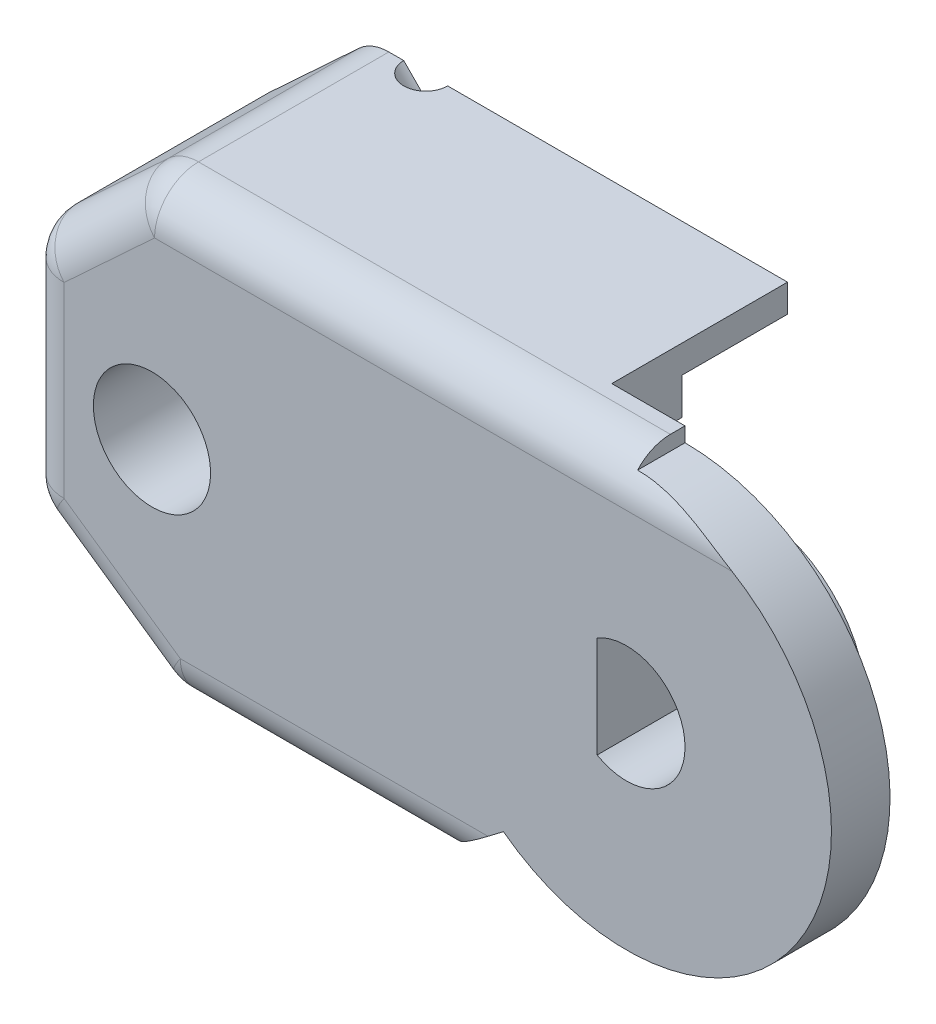
SolidWorks part; units mm, degrees
ref_plane "Front Plane" through (0, 0, 0) normal (0, 0, 1) x (1, 0, 0)
ref_plane "Top Plane" through (0, 0, 0) normal (0, 1, 0) x (1, 0, 0)
ref_plane "Right Plane" through (0, 0, 0) normal (1, 0, 0) x (0, 0, -1)
sketch "Sketch2" plane through (0, 0, 0) normal (0, 0, 1) x (1, 0, 0)
  line L1 (-2.5, 7.5) -> (-16.7, 7.5)
  line L2 (-20.7, 3.7934) -> (-20.7, -4.0316)
  line L3 (-15.7, -7.5) -> (-6.7, -7.5)
  line L4 (-6.7, -7.5) -> (-4.2, -5.6)
  line L5 (-2.5, 7.5) -> (0, 7.5)
  line L7 (0, 7) -> (0, 7.5)
  line L8 (-20.7, 3.7934) -> (-16.7, 7.5)
  line L9 (-20.7, -4.0316) -> (-15.7, -7.5)
  arc A1 (-4.2, -5.6) -> (7, 0) centre (0, 0) ccw
  arc A2 (7, 0) -> (0, 7) centre (0, 0) ccw
  dimension "D1" = 7
  dimension "D2" = 4
  dimension "D3" = 5
  dimension "D4" = 7.5
  dimension "D5" = 15
  dimension "D7" = 2.5
  dimension "D8" = 14
extrude "Boss-Extrude1" add sketch "Sketch2" along normal blind 2 contours A1 A2 L7 L5 L1 L8 L2 L9 L3 L4
sketch "Sketch4" plane through (0, 0, 2) normal (0, 0, 1) x (1, 0, 0)
  line L7 (-15.7, -7.5) -> (-6.7, -7.5)
  line L8 (-6.7, -7.5) -> (-6.7591, -4.5)
  line L9 (-6.7591, -4.5) -> (-12.2, -4.5)
  line L10 (-16.7, 7.5) -> (-2.5, 7.5)
  line L13 (-6.6963, 2) -> (-6.6963, 5.3)
  line L14 (-6.6963, 5.3) -> (-2.5, 5.3)
  line L21 (-20.7, -4.0316) -> (-15.7, -7.5)
  line L24 (-16.7, 7.5) -> (-20.7, 3.7934)
  line L25 (-20.7, -4.0316) -> (-20.7, 3.7934)
  line L26 (-12.2, 2) -> (-6.6963, 2)
  line L29 (-12.2, 2) -> (-12.2, -4.5)
  line L30 (-2.5, 7.5) -> (-2.5, 5.3)
  dimension "D1" = 8.5
  dimension "D2" = 2.5
  dimension "D3" = 3
extrude "Boss-Extrude2" add sketch "Sketch4" along normal blind 6
ref_point "Point1"
sketch "Sketch22" plane through (0, 0, 2) normal (0, 0, 1) x (1, 0, 0)
  line L0 (0, 5.3) -> (-14, 5.3) construction
  line L1 (0, 4) -> (-14, 4) construction
  line L2 (-14, 4) -> (-14, 5.3) construction
  circle A0 centre (0, 0) radius 5.3 construction
  circle A1 centre (0, 0) radius 4 construction
  dimension "D1" = 14
  dimension "D2" = 10.6
  dimension "D3" = 8
sketch "Sketch24" plane through (0, 0, 2) normal (0, 0, 1) x (1, 0, 0)
  circle A0 centre (0, 0) radius 3.9
  dimension "D1" = 7.8
extrude "Boss-Extrude5" add sketch "Sketch24" along normal blind 2.3
sketch "Sketch29" plane through (-6.6963, 0, 0) normal (1, 0, 0) x (0, 0, -1)
  line L0 (-1.9279, 3.9758) -> (-8, 3.9758) construction
  line L1 (-8, 2) -> (-8, 5.3) construction
sketch "Sketch30" plane through (-6.6963, 0, 0) normal (1, 0, 0) x (0, 0, -1)
  line L0 (-4.4659, 3.9758) -> (-4.4659, 5.3)
  line L1 (-4.4659, 3.9758) -> (-2.0573, 3.9758)
  line L2 (-4.4659, 5.3) -> (-2.0573, 5.3)
  line L3 (-2.0573, 3.9758) -> (-2.0573, 5.3)
  line L4 (-1.9279, 3.9758) -> (-8, 3.9758) construction
  line L5 (-8, 5.3) -> (-2, 5.3) construction
extrude "Cut-Extrude12" cut sketch "Sketch30" against normal blind 8
ref_plane "Plane1" through (0, 0, 8) normal (0, 0, 1) x (1, 0, 0)
sketch "Sketch8" plane through (0, 0, 2) normal (0, 0, 1) x (1, 0, 0)
  circle A1 centre (0, 0) radius 3.8
  circle A2 centre (0, 0) radius 2.5
sketch "Sketch28" plane through (0, 0, 4.3) normal (0, 0, 1) x (1, 0, 0)
  line L0 (-1, 1.7321) -> (-1, -1.7321)
  arc A0 (-1, -1.7321) -> (-1, 1.7321) centre (0, 0) ccw
  dimension "D1" = 1
  dimension "D2" = 2
extrude "Cut-Extrude11" cut sketch "Sketch28" against normal through all
sketch "Sketch33" plane through (0, 0, 8) normal (0, 0, 1) x (1, 0, 0)
  line L0 (-9.4481, 2) -> (-2.4157, -5.1566) construction
  line L1 (-12.2, 2) -> (-6.6963, 2) construction
  line L2 (-10.4836, -4.5) -> (-4.8246, 3.0469) construction
  line L3 (-6.7591, -4.5) -> (-12.2, -4.5) construction
fillet "Fillet1" radius 1.5 9 edges at (-11.2, -7.5, 0) (-8.35, 7.5, 0) (-18.7, 5.6467, 0) (-18.2, -5.7658, 0) (-20.7, -0.1191, 0) (-15.7, -7.5, 4) (-20.7, -4.0316, 4) (-20.7, 3.7934, 4) (-16.7, 7.5, 4)
sketch "Sketch34" plane through (0, 2, 0) normal (0, -1, 0) x (1, 0, 0)
  circle A0 centre (-9.4481, 8) radius 0.75
  dimension "D1" = 1.5
extrude "Cut-Extrude13" cut sketch "Sketch34" along direction (0.7009, -0.7133, 0) on the side against the normal blind 8
sketch "Sketch35" plane through (0, -4.5, 0) normal (0, 1, 0) x (1, 0, 0)
  circle A0 centre (-10.4836, -8) radius 0.75
extrude "Cut-Extrude14" cut sketch "Sketch35" along direction (0.5999, 0.8001, 0) on the side against the normal blind 8
sketch "Sketch36" plane through (0, 0, 8) normal (0, 0, 1) x (1, 0, 0)
  line L2 (-12.2, -4.5) -> (-12.2, 2) construction
  circle A0 centre (-16.2, 0) radius 0.95
  dimension "D1" = 4
extrude "Cut-Extrude15" cut sketch "Sketch36" against normal blind 8
sketch "Sketch37" plane through (0, 0, 0) normal (0, 0, -1) x (-1, 0, 0)
  circle A0 centre (16.2, 0) radius 2
extrude "Cut-Extrude16" cut sketch "Sketch37" against normal blind 5
sketch "Sketch38" plane through (0, 0, 8) normal (0, 0, 1) x (1, 0, 0)
  line L0 (-6.6963, 5.3) -> (-2.5, 5.3)
  line L1 (-6.6963, 5.3) -> (-6.6963, 6.55)
  line L2 (-2.5, 5.3) -> (-2.5, 6.55)
  line L3 (-6.6963, 6.55) -> (-2.5, 6.55)
  dimension "D1" = 1.25
extrude "Cut-Extrude17" cut sketch "Sketch38" against normal blind 3.6
mirror "Mirror1" about plane through (0, 0, 8) normal (0, 0, 1) of bodies 129
split "Split1" trim tools "Plane1" bodies to split 130 resulting bodies 131 132
delete or keep bodies "Body-Delete/Keep 1" type delete bodies bodies 131
